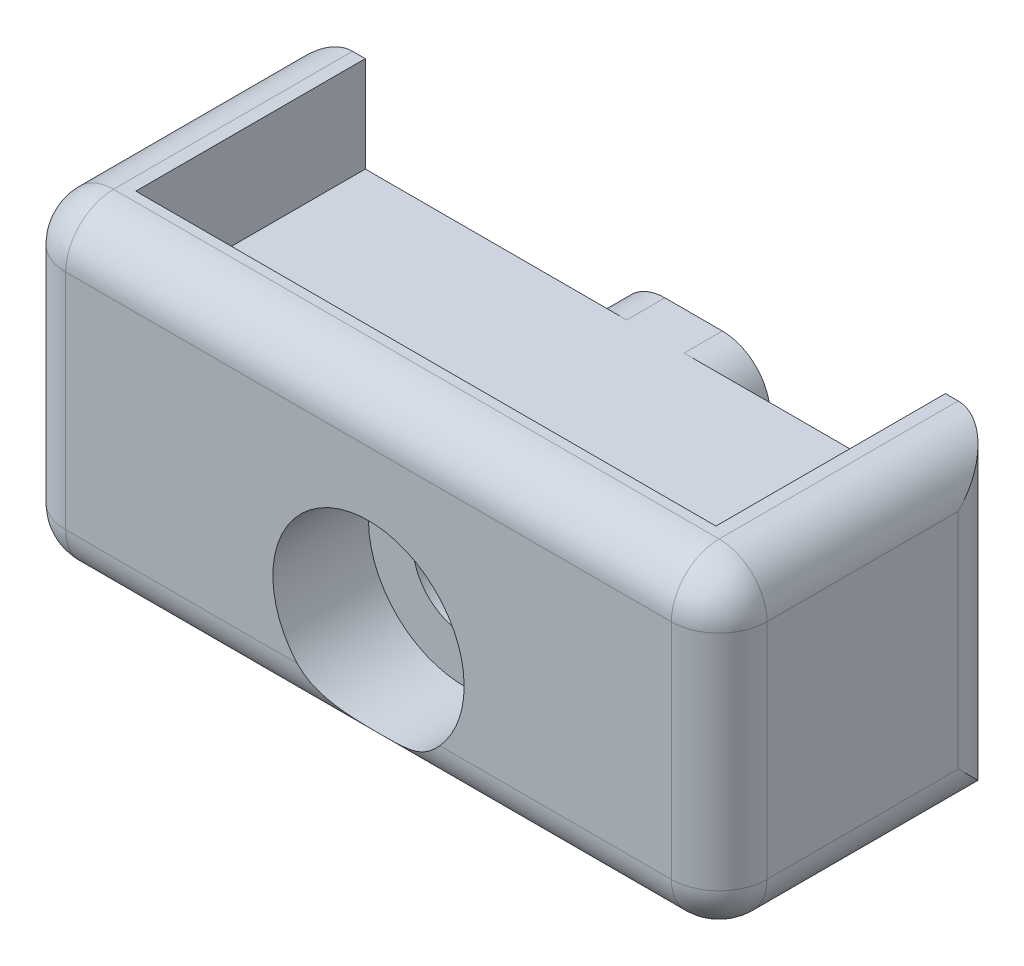
SolidWorks part; units mm, degrees
material "ABS"
ref_plane "Plan de face" through (0, 0, 0) normal (0, 0, 1) x (1, 0, 0)
ref_plane "Plan de dessus" through (0, 0, 0) normal (0, 1, 0) x (1, 0, 0)
ref_plane "Plan de droite" through (0, 0, 0) normal (1, 0, 0) x (0, 0, -1)
sketch "Esquisse1" plane through (0, 0, 0) normal (0, 1, 0) x (1, 0, 0)
  line L0 (2.4, 0) -> (11, 0)
  line L1 (-11, 0) -> (-2.4, 0)
  line L2 (-11, 0) -> (-11, -9)
  line L3 (-11, -9) -> (11, -9)
  line L4 (11, 0) -> (11, -9)
  line L5 (-2.4, 1.2) -> (2.4, 1.2)
  line L6 (-2.4, 1.2) -> (-2.4, 0)
  line L8 (2.4, 1.2) -> (2.4, 0)
  point P5 (0, -9)
  dimension "D1" = 4.8
  dimension "D2" = 22
  dimension "D3" = 9
  dimension "D4" = 1.2
extrude "Boss.-Extru.1" add sketch "Esquisse1" along normal blind 10
sketch "Esquisse2" plane through (0, 10, 0) normal (0, 1, 0) x (1, 0, 0)
  line L0 (2.4, 1.2) -> (-2.4, 1.2) construction
  line L1 (-9.1, 1.2) -> (9.1, 1.2)
  line L2 (-9.1, 1.2) -> (-9.1, -7.2)
  line L3 (-9.1, -7.2) -> (9.1, -7.2)
  line L4 (9.1, 1.2) -> (9.1, -7.2)
  line L5 (-11, 0) -> (-11, -9) construction
  line L6 (-11, -9) -> (11, -9) construction
  line L7 (11, 0) -> (2.4, 0) construction
  point P4 (0, 1.2)
  dimension "D1" = 1.9
  dimension "D2" = 1.8
  dimension "D3" = 18.2
  dimension "D4" = 7.2
extrude "Enlèv. mat.-Extru.1" cut sketch "Esquisse2" against normal blind 3
sketch "Esquisse3" plane through (0, 0, -1.2) normal (0, 0, -1) x (-1, 0, 0)
  line L0 (2.4, 7) -> (2.4, 0) construction
  circle A0 centre (0, 3.5) radius 1.6
  point P4 (2.4, 3.5)
  dimension "D1" = 3.2
extrude "Enlèv. mat.-Extru.2" cut sketch "Esquisse3" against normal through all
sketch "Esquisse4" plane through (0, 0, 9) normal (0, 0, 1) x (1, 0, 0)
  circle A0 centre (0, 3.5) radius 3
  circle A1 centre (0, 3.5) radius 1.6 construction
  dimension "D1" = 6
extrude "Enlèv. mat.-Extru.3" cut sketch "Esquisse4" against normal blind 3
fillet "Congé1" radius 1.5 14 edges at (-11, 5, 0) (11, 5, 0) (-2.4, 7, -0.6) (2.4, 7, -0.6) (2.4, 0, -0.6) (-2.4, 0, -0.6) (11, 0, 4.5) (-11, 0, 4.5) (0, 0, 9) (11, 5, 9) (-11, 5, 9) (-11, 10, 4.5) (0, 10, 9) (11, 10, 4.5)
